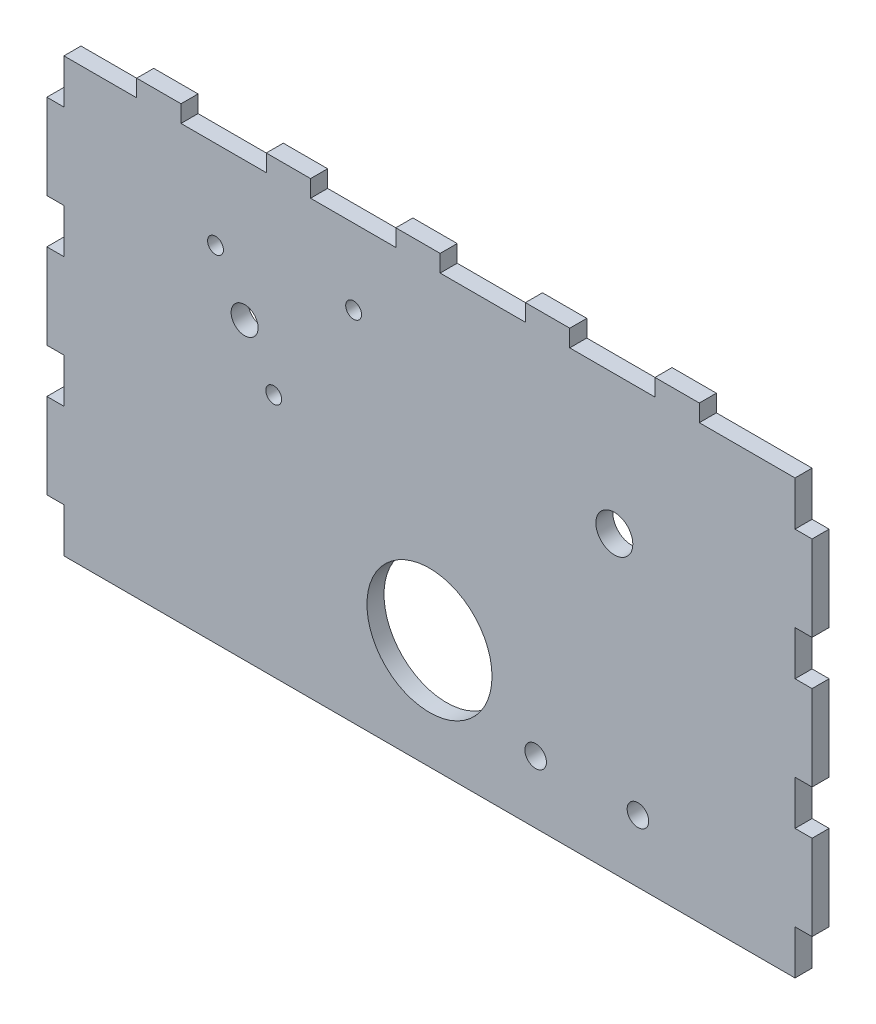
SolidWorks part; units mm, degrees
material "ENPH 253 Hardboard"
ref_plane "Front Plane" through (0, 0, 0) normal (0, 0, 1) x (1, 0, 0)
ref_plane "Top Plane" through (0, 0, 0) normal (0, 1, 0) x (1, 0, 0)
ref_plane "Right Plane" through (0, 0, 0) normal (1, 0, 0) x (0, 0, -1)
sketch "Sketch1" plane through (0, 0, 0) normal (0, 0, 1) x (1, 0, 0)
  line L1 (-67.32, 38.1) -> (67.32, 38.1)
  line L2 (-67.32, 38.1) -> (-67.32, -38.1)
  line L3 (-67.32, -38.1) -> (67.32, -38.1)
  line L4 (67.32, 38.1) -> (67.32, -38.1)
  line L5 (-67.32, 38.1) -> (67.32, -38.1) construction
  line L6 (-67.32, -38.1) -> (67.32, 38.1) construction
  point P0 (0, 0)
  dimension "D1" = 134.64
  dimension "D2" = 76.2
extrude "Boss-Extrude1" add sketch "Sketch1" along normal blind 3
sketch "Sketch2" plane through (0, 0, 3) normal (0, 0, 1) x (1, 0, 0)
  line L1 (-67.32, 38.1) -> (-64.32, 38.1)
  line L2 (-67.32, 38.1) -> (-67.32, 30.3)
  line L3 (-67.32, 30.3) -> (-64.32, 30.3)
  line L4 (-64.32, 38.1) -> (-64.32, 30.3)
  dimension "D1" = 3
  dimension "D2" = 7.8
extrude "Cut-Extrude1" cut sketch "Sketch2" against normal through all
pattern_linear "LPattern1" count 4 spacing 22.8 along (0, -1, 0) of "Cut-Extrude1"
mirror "Mirror4" about plane through (0, 0, 0) normal (1, 0, 0) of "LPattern1"
sketch "Sketch3" plane through (0, 38.1, 0) normal (0, 1, 0) x (1, 0, 0)
  line L0 (64.32, 0) -> (-64.32, 0) construction
  line L1 (-43.72, 0) -> (-51.52, 0)
  line L2 (-43.72, 0) -> (-43.72, -3)
  line L3 (-43.72, -3) -> (-51.52, -3)
  line L4 (-51.52, 0) -> (-51.52, -3)
  line L5 (64.32, -3) -> (-64.32, -3) construction
  line L6 (-64.32, 0) -> (-64.32, -3) construction
  dimension "D1" = 12.8
  dimension "D2" = 7.8
extrude "Boss-Extrude2" add sketch "Sketch3" along normal blind 3
pattern_linear "LPattern2" count 5 spacing 22.8 along (1, 0, 0) of "Boss-Extrude2"
sketch "Sketch4" plane through (0, 0, 3) normal (0, 0, 1) x (1, 0, 0)
  line L0 (-64.32, -38.1) -> (64.32, -38.1) construction
  line L1 (-64.32, -38.1) -> (-64.32, -30.3) construction
  circle A0 centre (0, -18.8) radius 11
  dimension "D1" = 22
  dimension "D2" = 19.3
  dimension "D3" = 64.32
extrude "Cut-Extrude2" cut sketch "Sketch4" against normal through all
sketch "Sketch5" plane through (0, 0, 3) normal (0, 0, 1) x (1, 0, 0)
  line L0 (0, -18.8) -> (-36.8059, -18.8) construction
  line L1 (-32.5269, 13.7269) -> (0, -18.8) construction
  line L2 (0, -18.8) -> (32.5269, 13.7269) construction
  circle A0 centre (32.5269, 13.7269) radius 3.25
  circle A1 centre (-32.5269, 13.7269) radius 2.3749
  dimension "D1" = 4.7498
  dimension "D2" = 6.5
  dimension "D3" = 46
  dimension "D4" = 46
  dimension "D5" = 45
  dimension "D6" = 90
extrude "Cut-Extrude3" cut sketch "Sketch5" against normal through all
hole_wizard "#6 Clearance Hole1" positions "Sketch7" profile "Sketch8" hole size "#6" standard "ANSI Inch" end condition up to next
sketch "Sketch7" plane through (0, 0, 3) normal (0, 0, 1) x (1, 0, 0)
  point P0 (36.68, -27.1)
  point P3 (18.68, -27.1)
sketch "Sketch8" plane through (36.68, -27.1, 3) normal (1, 0, 0) x (0, -1, 0)
  line L0 (0, 0) -> (0, 3)
  line L1 (0, 3) -> (1.8986, 3)
  line L2 (1.8986, 3) -> (1.8986, 0)
  line L5 (1.8986, 0) -> (0, 0)
  line L11 (0, -6.35) -> (0, 107.95) construction
  dimension "Thru Hole Dia." = 3.7973
  dimension "Thru Hole Depth" = 3
hole_wizard "#3 Clearance Hole1" positions "Sketch9" profile "Sketch10" hole size "#3" standard "ANSI Inch" end condition up to next
sketch "Sketch9" plane through (0, 0, 3) normal (0, 0, 1) x (1, 0, 0)
  point P4 (-37.6485, 22.5604)
  point P7 (-27.4053, 4.8935)
  point P15 (-13.3438, 24.8491)
sketch "Sketch10" plane through (-37.6485, 22.5604, 3) normal (1, 0, 0) x (0, -1, 0)
  line L0 (0, 0) -> (0, 3)
  line L1 (0, 3) -> (1.397, 3)
  line L2 (1.397, 3) -> (1.397, 0)
  line L5 (1.397, 0) -> (0, 0)
  line L11 (0, -6.35) -> (0, 107.95) construction
  dimension "Thru Hole Dia." = 2.794
  dimension "Thru Hole Depth" = 3
